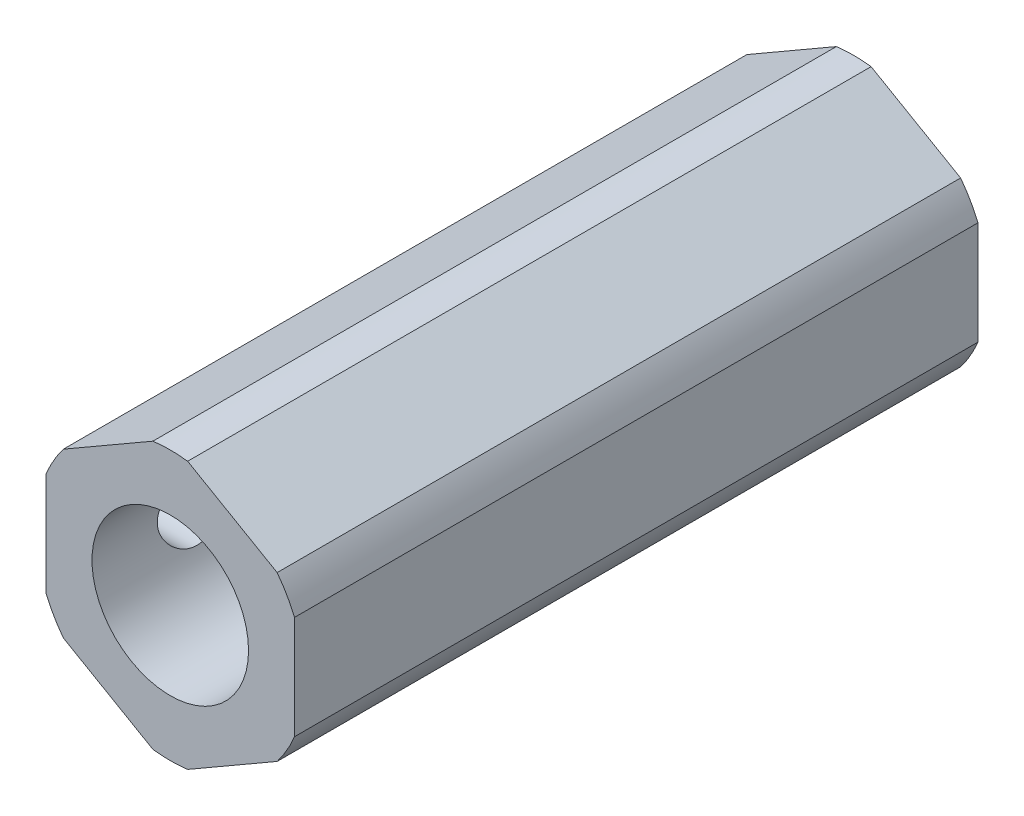
SolidWorks part; units mm, degrees
material "ThunderHex"
ref_plane "Front Plane" through (0, 0, 0) normal (0, 0, 1) x (1, 0, 0)
ref_plane "Top Plane" through (0, 0, 0) normal (0, 1, 0) x (1, 0, 0)
ref_plane "Right Plane" through (0, 0, 0) normal (1, 0, 0) x (0, 0, -1)
ref_plane "End1" through (0, 0, 17.4625) normal (0, 0, 1) x (1, 0, 0)
ref_plane "End2" through (0, 0, -17.4625) normal (0, 0, 1) x (1, 0, 0)
sketch "Sketch1" plane through (0, 0, 0) normal (0, 0, 1) x (1, 0, 0)
  circle A0 centre (0, 0) radius 6.35
  dimension "D1" = 12.7
extrude "Basic Rod" add sketch "Sketch1" along normal up to surface (17.4625 mm away) and the other way up to surface (17.4625 mm away) up to plane "End1" other way up to plane "End2"
ref_axis "Center Axis" through (0, 0, -38.2778) along (0, 0, 1)
sketch "Sketch8" plane through (0, 0, 0) normal (0, 0, 1) x (1, 0, 0)
  line L0 (-5.4616, 4.1791) -> (-6.35, 3.6662) construction
  line L1 (-0.8884, 6.8194) -> (-5.4616, 4.1791)
  line L2 (-6.35, 2.6403) -> (-6.35, -2.6403)
  line L3 (-5.4616, -4.1791) -> (-0.8884, -6.8194)
  line L4 (0.8884, -6.8194) -> (5.4616, -4.1791)
  line L5 (6.35, -2.6403) -> (6.35, 2.6403)
  line L6 (5.4616, 4.1791) -> (0.8884, 6.8194)
  line L7 (-6.35, 3.6662) -> (-6.35, 2.6403) construction
  line L8 (0, 7.3323) -> (-0.8884, 6.8194) construction
  line L9 (0.8884, 6.8194) -> (0, 7.3323) construction
  line L10 (6.35, 3.6662) -> (5.4616, 4.1791) construction
  line L11 (6.35, 2.6403) -> (6.35, 3.6662) construction
  line L12 (6.35, -3.6662) -> (6.35, -2.6403) construction
  line L13 (5.4616, -4.1791) -> (6.35, -3.6662) construction
  line L14 (0, -7.3323) -> (0.8884, -6.8194) construction
  line L15 (-0.8884, -6.8194) -> (0, -7.3323) construction
  line L16 (-6.35, -3.6662) -> (-5.4616, -4.1791) construction
  line L17 (-6.35, -2.6403) -> (-6.35, -3.6662) construction
  circle A0 centre (0, 0) radius 6.35 construction
  arc A1 (-6.35, -2.6403) -> (-5.4616, -4.1791) centre (0, 0) ccw
  circle A2 centre (0, 0) radius 6.35 construction
  arc A3 (-6.35, 2.6403) -> (-6.35, -2.6403) centre (0, 0) ccw construction
  arc A4 (-0.8884, 6.8194) -> (-5.4616, 4.1791) centre (0, 0) ccw construction
  arc A5 (-5.4616, 4.1791) -> (-6.35, 2.6403) centre (0, 0) ccw
  arc A6 (5.4616, 4.1791) -> (0.8884, 6.8194) centre (0, 0) ccw construction
  arc A7 (0.8884, 6.8194) -> (-0.8884, 6.8194) centre (0, 0) ccw
  arc A8 (6.35, -2.6403) -> (6.35, 2.6403) centre (0, 0) ccw construction
  arc A9 (6.35, 2.6403) -> (5.4616, 4.1791) centre (0, 0) ccw
  arc A10 (0.8884, -6.8194) -> (5.4616, -4.1791) centre (0, 0) ccw construction
  arc A11 (5.4616, -4.1791) -> (6.35, -2.6403) centre (0, 0) ccw
  arc A12 (-5.4616, -4.1791) -> (-0.8884, -6.8194) centre (0, 0) ccw construction
  arc A13 (-0.8884, -6.8194) -> (0.8884, -6.8194) centre (0, 0) ccw
  dimension "D1" = 13.7541
extrude "THex" add sketch "Sketch8" along normal mid plane 34.925
sketch "Sketch5" plane through (0, 0, 0) normal (0, 0, 1) x (1, 0, 0)
  line L1 (-3.6662, 6.35) -> (-7.3323, 0)
  line L2 (-7.3323, 0) -> (-3.6662, -6.35)
  line L3 (-3.6662, -6.35) -> (3.6662, -6.35)
  line L4 (3.6662, -6.35) -> (7.3323, 0)
  line L5 (7.3323, 0) -> (3.6662, 6.35)
  line L6 (3.6662, 6.35) -> (-3.6662, 6.35)
  circle A0 centre (0, 0) radius 6.35 construction
  circle A2 centre (0, 0) radius 6.35 construction
extrude "Hex" [suppressed] add sketch "Sketch5" along normal mid plane 34.925
sketch "Sketch7" plane through (0, 0, 0) normal (1, 0, 0) x (0, 0, -1)
  line L0 (0, 0) -> (-50000, 0) construction
  line L1 (-17.4625, 5.9436) -> (-18.4785, 5.9436)
  line L2 (-18.4785, 5.9436) -> (-18.4785, 6.35)
  line L3 (-18.4785, 6.35) -> (-19.4945, 6.35)
  line L4 (-20.0025, 5.842) -> (-20.0025, 0)
  line L5 (-20.0025, 0) -> (-17.4625, 0)
  line L6 (-17.4625, 0) -> (-17.4625, 5.9436)
  line L7 (-19.4945, 6.35) -> (-20.0025, 5.842)
  line L8 (38.2778, 0) -> (-38.2778, 0) construction
  line L9 (-17.4625, 5.2388) -> (-17.4625, -5.2388) construction
  point P7 (-20.0025, 6.35)
  dimension "D1" = 12.7
  dimension "D4" = 1.016
  dimension "D2" = 0.4064
  dimension "D3" = 2.54
revolve "1stSnapRing" [suppressed] add sketch "Sketch7" angle 360 about axis through (0, 0, -38.2778) along (0, 0, 1)
mirror "2ndSnapRing" [suppressed] about plane through (0, 0, 0) normal (0, 0, 1)
sketch "Sketch2" plane through (0, 0, 0) normal (0, 0, 1) x (1, 0, 0)
  circle A0 centre (0, 0) radius 2.1158
  dimension "D1" = 4.2316
extrude "Internal Cut" cut sketch "Sketch2" against normal through all both and the other way through all
sketch "Sketch9" plane through (0, 0, 17.4625) normal (0, 0, 1) x (1, 0, 0)
  circle A0 centre (0, 0) radius 4
  dimension "D1" = 8
extrude "Cut-Extrude1" cut sketch "Sketch9" against normal blind 20
sketch "Sketch10" plane through (-6.35, 0, 0) normal (-1, 0, 0) x (0, 0, 1)
  line L0 (17.4625, 0) -> (12.4612, 0) construction
  line L1 (17.4625, 2.6403) -> (17.4625, -2.6403) construction
  line L2 (12.4612, 0) -> (4.4602, 0) construction
  circle A0 centre (4.4602, 0) radius 1.6662
  circle A1 centre (12.4612, 0) radius 1.6662
  dimension "D1" = 3.3325
  dimension "D2" = 5.0013
  dimension "D3" = 8.001
extrude "Cut-Extrude2" cut sketch "Sketch10" against normal up to next
equation "\"Unit Measure\"= \"Length\"'in"
equation "\"D1@Sketch1\"=\"OD\""
equation "\"D1\"= \"Length\""
equation "\"D1@Sketch2\"=\"ID\""
equation "\"Internal Cut\"= IIF ( \"ID\" = 0 ,  suppressed  ,  unsuppressed  ) "
equation "\"D1@Hex\" = \"Length\""
equation "\"Hex\" = IIF ( \"SelectionType\" = 1 , \"suppressed\" , iif ( \"SelectionType\" = 2 , \"suppressed\" , \"unsuppressed\" ) )"
equation "\"OutsideDiameter\"= \"OD\"'in"
equation "\"ThunderHexDia\"= iif ( \"OD\" < .36 , \"OD\" * 1.1 , iif ( \"OD\" < .40 , .4035 , iif ( \"OD\" < .52 , .5415 , \"OD\" * 1.1 ) ) )"
equation "\"D1@Sketch7\"=\"Thickness\""
equation "\"SRDia\"= iif ( \"OD\" = .5 , ( \"OD\" - .468 ) / 2 , iif ( \"OD\" = .375 , ( \"OD\" - .352 ) / 2 , .050 ) )"
equation "\"D2@Sketch7\"= \"SnapRingDepth\""
equation "\"1stSnapRing\"= iif ( \"SnapRingCount\" > 0 , \"unsuppressed\" , \"suppressed\" )"
equation "\"2ndSnapRing\"= iif ( \"SnapRingCount\" = 2 , \"unsuppressed\" , \"suppressed\" )"
equation "\"D1@End1\" = \"Length\" / 2"
equation "\"D1@End2\" = \"Length\""
equation "\"D1@Sketch8\"=\"ThunderHexDia\""
equation "\"D1@THex\" = \"Length\""
equation "\"THex\"= IIF ( \"SelectionType\" = 0 ,  suppressed  , iif ( \"SelectionType\" = 2 ,  suppressed  ,  unsuppressed  )  ) "
